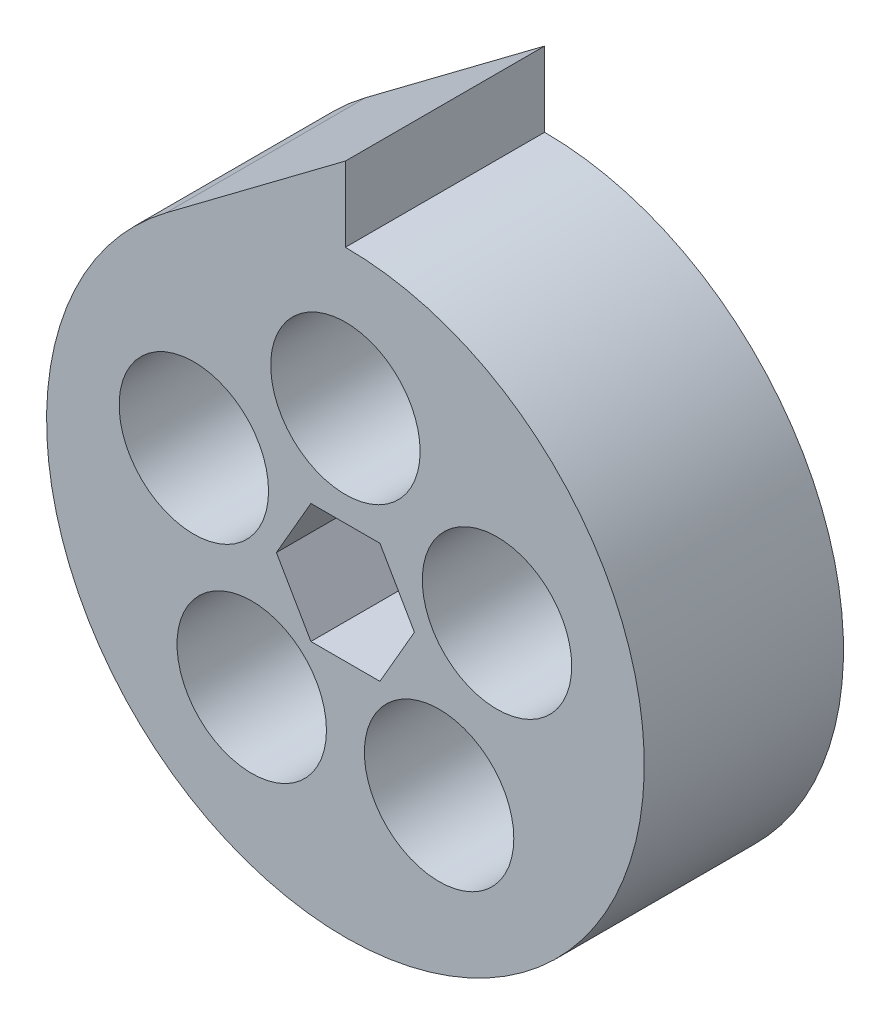
SolidWorks part; units mm, degrees
material "Commercially Pure titanium (Ti-55)  UNS R50550*"
ref_plane "Front Plane" through (0, 0, 0) normal (0, 0, 1) x (1, 0, 0)
ref_plane "Top Plane" through (0, 0, 0) normal (0, 1, 0) x (1, 0, 0)
ref_plane "Right Plane" through (0, 0, 0) normal (1, 0, 0) x (0, 0, -1)
sketch "Sketch3" plane through (0, 0, 0) normal (0, 0, 1) x (1, 0, 0)
  line L0 (0, 30) -> (0, 37.5)
  line L3 (0, 37.5) -> (-18, 24)
  line L6 (6.9282, 0) -> (3.4641, 6)
  line L7 (3.4641, 6) -> (-3.4641, 6)
  line L8 (-3.4641, 6) -> (-6.9282, 0)
  line L9 (-6.9282, 0) -> (-3.4641, -6)
  line L10 (-3.4641, -6) -> (3.4641, -6)
  line L11 (3.4641, -6) -> (6.9282, 0)
  arc A2 (-18, 24) -> (0, 30) centre (0, 0) ccw
  circle A3 centre (0, 0) radius 6 construction
  circle A4 centre (0, 16) radius 7.5
  circle A5 centre (15.2169, 4.9443) radius 7.5
  circle A6 centre (9.4046, -12.9443) radius 7.5
  circle A7 centre (-9.4046, -12.9443) radius 7.5
  circle A8 centre (-15.2169, 4.9443) radius 7.5
  point P3 (0, 0)
  point P15 (0, 0)
  point P16 (0, 0)
  point P25 (0, 0)
  dimension "D2" = 7.5
  dimension "D1" = 60
  dimension "D4" = 15
  dimension "D3" = 12
  dimension "D5" = 16
  dimension "D6" = 5
extrude "Boss-Extrude1" add sketch "Sketch3" along normal blind 20
